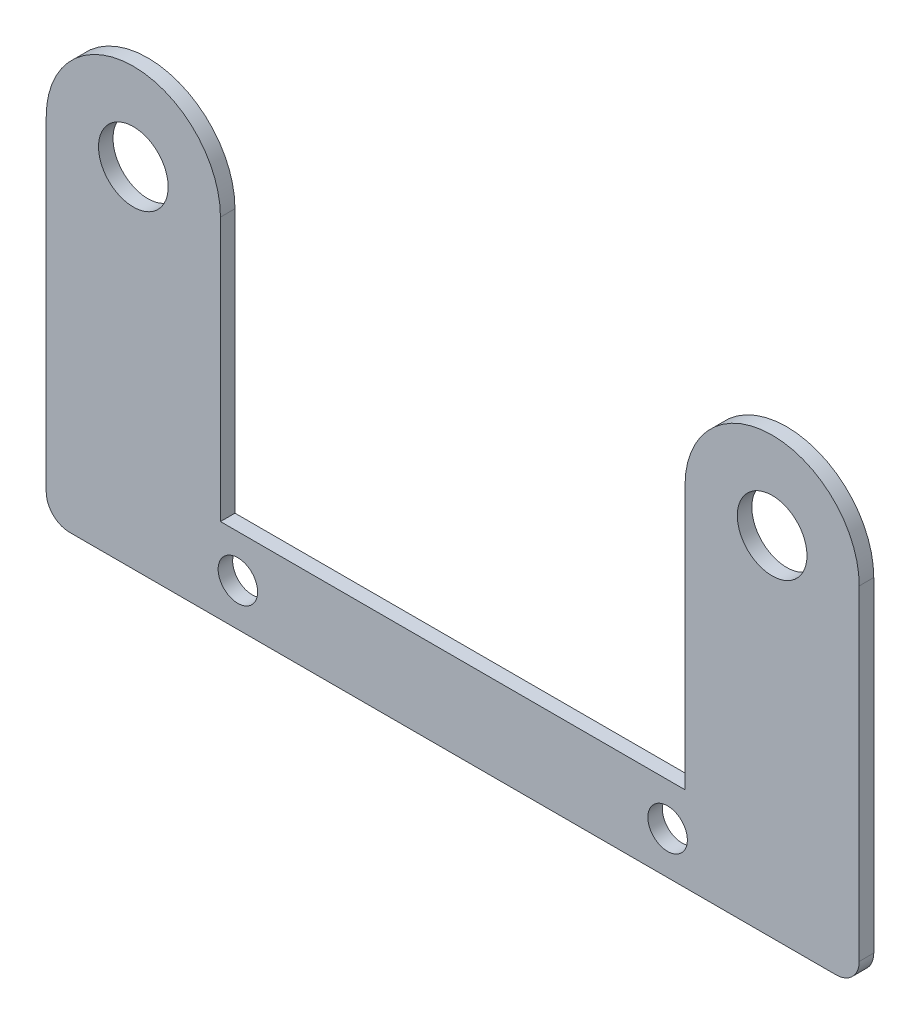
SolidWorks part; units mm, degrees
ref_plane "Front Plane" through (0, 0, 0) normal (0, 0, 1) x (1, 0, 0)
ref_plane "Top Plane" through (0, 0, 0) normal (0, 1, 0) x (1, 0, 0)
ref_plane "Right Plane" through (0, 0, 0) normal (1, 0, 0) x (0, 0, -1)
sketch "Sketch1" plane through (0, 0, 0) normal (0, 0, 1) x (1, 0, 0)
  line L0 (0, 38.1) -> (19.05, 38.1) construction
  line L2 (0, 38.1) -> (0, 0)
  line L3 (0, 0) -> (88.9, 0)
  line L4 (88.9, 38.1) -> (88.9, 0)
  line L5 (19.05, 38.1) -> (19.05, 9.271)
  line L6 (19.05, 9.271) -> (69.85, 9.271)
  line L7 (69.85, 9.271) -> (69.85, 38.1)
  line L8 (69.85, 38.1) -> (88.9, 38.1) construction
  line L10 (20.955, 4.6355) -> (67.945, 4.6355) construction
  line L11 (44.45, 9.271) -> (44.45, 0) construction
  circle A0 centre (20.955, 4.6355) radius 2.159
  circle A1 centre (67.945, 4.6355) radius 2.159
  circle A2 centre (9.525, 38.1) radius 3.81
  circle A3 centre (79.375, 38.1) radius 3.81
  arc A4 (0, 38.1) -> (19.05, 38.1) centre (9.525, 38.1) cw
  arc A5 (69.85, 38.1) -> (88.9, 38.1) centre (79.375, 38.1) cw
  point P0 (44.45, 4.6355)
  dimension "D1" = 4.318
  dimension "D5" = 7.62
  dimension "D2" = 46.99
  dimension "D3" = 88.9
  dimension "D4" = 9.271
  dimension "D6" = 38.1
  dimension "D8" = 19.05
extrude "Boss-Extrude1" add sketch "Sketch1" along normal blind 1.5875
fillet "Fillet1" radius 2.54 2 edges at (88.9, 0, 0.7937) (0, 0, 0.7937)
